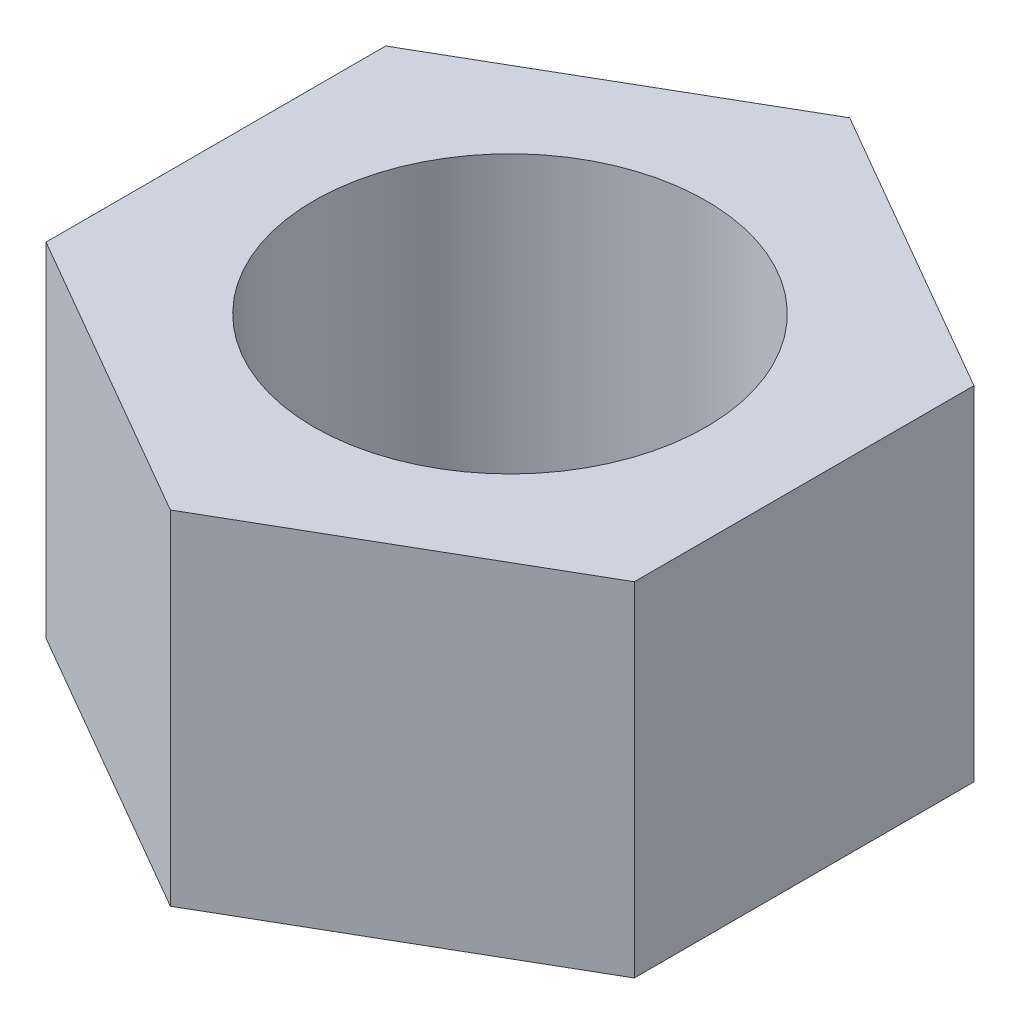
SolidWorks part; units mm, degrees
ref_plane "Front Plane" through (0, 0, 0) normal (0, 0, 1) x (1, 0, 0)
ref_plane "Top Plane" through (0, 0, 0) normal (0, 1, 0) x (1, 0, 0)
ref_plane "Right Plane" through (0, 0, 0) normal (1, 0, 0) x (0, 0, -1)
sketch "Sketch1" plane through (0, 0, 0) normal (0, 0, 1) x (1, 0, 0)
  line L0 (0, -4.1672) -> (0, 4.1672) construction
  line L1 (7.1438, 0) -> (-7.1438, 0) construction
  line L2 (4.7625, -4.1672) -> (-4.7625, -4.1672) construction
  line L3 (4.7625, -4.1672) -> (4.7625, -3.1089) construction
  point P4 (0, 0)
  point P8 (0, 0)
  point P11 (0, -4.1672)
  dimension "Height" = 8.3344
  dimension "Width" = 14.2875
  dimension "Thread Size" = 9.525
  dimension "Thread Pitch" = 1.0583
sketch "Sketch2" plane through (0, 0, 0) normal (1, 0, 0) x (0, 0, -1)
  line L0 (0, -4.1672) -> (0, 4.1672) construction
  line L1 (3.048, -1.9542) -> (-3.048, -1.9542)
  line L2 (3.048, -1.9542) -> (3.048, 4.1672)
  line L3 (3.048, 4.1672) -> (-3.048, 4.1672)
  line L4 (-3.048, -1.9542) -> (-3.048, 4.1672)
  line L5 (3.048, -1.9542) -> (-3.048, 4.1672) construction
  line L6 (3.048, 4.1672) -> (-3.048, -1.9542) construction
  point P0 (0, 1.1065)
  point P7 (0, 4.1672)
  dimension "Minimum Slot Width" = 6.096
  dimension "Minimum Slot Depth" = 6.1214
sketch "Sketch11" plane through (0, 0, 0) normal (0, 1, 0) x (1, 0, 0)
  line L1 (0, 8.2489) -> (-7.1438, 4.1244)
  line L2 (-7.1438, 4.1244) -> (-7.1438, -4.1244)
  line L3 (-7.1438, -4.1244) -> (0, -8.2489)
  line L4 (0, -8.2489) -> (7.1438, -4.1244)
  line L5 (7.1438, -4.1244) -> (7.1438, 4.1244)
  line L6 (7.1438, 4.1244) -> (0, 8.2489)
  circle A0 centre (0, 0) radius 7.1438 construction
  circle A1 centre (0, 0) radius 4.7625
  point P19 (0, -4.7625)
extrude "Boss-Extrude1" add sketch "Sketch11" along normal up to vertex (4.1672 mm away) and the other way up to vertex (4.1672 mm away) up to point (0, 4.1672, 0) other way up to point (0, -4.1672, 0)
fillet "Fillet1" [suppressed] radius 0.4286
sketch "Sketch3" plane through (0, 0, 0) normal (1, 0, 0) x (0, 0, -1)
  line L1 (4.1244, 4.1672) -> (8.2489, 4.1672) construction
  line L2 (6.4294, -4.1672) -> (8.2489, -3.1167)
  line L3 (4.1244, -4.1672) -> (8.2489, -4.1672) construction
  line L4 (8.2489, 4.1672) -> (8.2489, -4.1672) construction
  line L5 (8.2489, -3.1167) -> (8.2489, -4.1672)
  line L7 (6.7151, 4.1672) -> (8.2489, 3.2817)
  line L8 (8.2489, 3.2817) -> (8.2489, 4.1672)
  line L10 (6.4294, -4.1672) -> (8.2489, -4.1672)
  line L12 (6.7151, 0) -> (7.1438, 0) construction
  line L16 (6.7151, 4.1672) -> (8.2489, 4.1672)
  line L21 (4.7625, -4.1672) -> (4.7625, -3.9291)
  line L22 (-4.1244, -4.1672) -> (4.1244, -4.1672) construction
  line L24 (5.0006, -4.1672) -> (4.7625, -4.1672)
  line L25 (4.7625, -3.9291) -> (5.0006, -4.1672)
  line L26 (4.7625, 4.1672) -> (4.7625, 3.9291)
  line L27 (4.7625, 4.1672) -> (5.0006, 4.1672)
  line L28 (5.0006, 4.1672) -> (4.7625, 3.9291)
  line L29 (3.048, 4.1672) -> (-3.048, 4.1672) construction
  line L30 (5.0006, 0) -> (5.4293, 0) construction
  line L31 (6.2865, 0) -> (6.7151, 0) construction
  line L32 (5.4293, 0) -> (5.8579, 0) construction
  line L33 (5.8579, 0) -> (6.2865, 0) construction
  point P0 (6.7151, 4.1672)
  point P1 (7.1438, 0)
  point P14 (4.7625, 0)
  point P36 (7.1438, -4.1672)
  point P44 (6.9294, 0)
  dimension "D2" = 30
  dimension "D5" = 0.2381
  dimension "D7" = 0.7144
  dimension "D1" = 30
revolve "Cut-Revolve2" [suppressed] cut sketch "Sketch3" angle 360 about L0
sketch "Sketch15" [suppressed] plane through (15.4781, 0, 17.1852) normal (0.5, 0, -0.866) x (-0.866, 0, -0.5)
  line L0 (21.997, 3.9197) -> (21.997, 2.0011) construction
  line L1 (21.997, -1.8361) -> (21.997, 0.0825) construction
  line L2 (21.997, 0.0825) -> (21.997, 2.0011) construction
  line L3 (21.997, -1.8361) -> (21.997, -3.7547) construction
  line L6 (20.8893, 0.0825) -> (21.4432, -0.8768)
  line L7 (21.4432, -0.8768) -> (22.5509, -0.8768)
  line L8 (22.5509, -0.8768) -> (23.1048, 0.0825)
  line L9 (23.1048, 0.0825) -> (22.5509, 1.0418)
  line L10 (22.5509, 1.0418) -> (21.4432, 1.0418)
  line L11 (21.4432, 1.0418) -> (20.8893, 0.0825)
  circle A0 centre (21.997, 0.0825) radius 0.9593 construction
  spline S4 degree 3 poles (17.8726, 3.2817) (18.546, 3.4761) (19.2244, 3.6363) (20.5953, 3.8583) (21.2879, 3.9193) (22.3398, 3.9199) (22.6921, 3.905) (23.389, 3.8469) (23.7351, 3.8037) (24.7673, 3.6369) (25.4472, 3.4763) (26.1215, 3.2817) knots 0 0 0 0 0.25 0.25 0.5 0.5 0.625 0.625 0.75 0.75 1 1 1 1 construction
  spline S5 degree 3 poles (26.1215, -3.1167) (25.448, -3.3111) (24.7697, -3.4713) (23.3988, -3.6933) (22.7062, -3.7543) (21.6543, -3.755) (21.302, -3.74) (20.6051, -3.6819) (20.259, -3.6387) (19.2268, -3.472) (18.5469, -3.3113) (17.8726, -3.1167) knots 0 0 0 0 0.25 0.25 0.5 0.5 0.625 0.625 0.75 0.75 1 1 1 1 construction
  point P1 (21.997, 1.0418)
  point P6 (21.997, 0)
extrude "Cut-Extrude2" [suppressed] cut sketch "Sketch15" along normal blind 0.1905
sketch "Sketch18" [suppressed] plane through (0, 4.1672, 0) normal (0, 1, 0) x (1, 0, 0)
  line L0 (0, 0) -> (0, -6.7151) construction
  line L1 (0, 0) -> (-4.1421, -4.1421) construction
  line L2 (0, 0) -> (-1.5161, -5.6583) construction
  line L3 (-6.7151, 0) -> (-6.3722, 0) construction
  line L4 (-6.3722, 0) -> (-6.0293, 0) construction
  line L5 (-6.0293, 0) -> (-5.6864, 0) construction
  line L6 (-5.6864, 0) -> (-5.3435, 0) construction
  line L7 (-5.3435, 0) -> (-5.0006, 0) construction
  line L8 (0, 0) -> (-3.5719, -6.1867) construction
  line L9 (-7.1437, -4.1244) -> (0, -8.2489) construction
  circle A0 centre (0, 0) radius 6.7151 construction
  circle A1 centre (0, 0) radius 5.0006 construction
  arc A2 (-4.1421, -4.1421) -> (-1.5161, -5.6583) centre (0, 0) ccw construction
  arc A3 (-4.2634, -4.2634) -> (-1.5605, -5.8239) centre (0, 0) ccw
  arc A4 (-4.0209, -4.0209) -> (-1.4718, -5.4927) centre (0, 0) ccw
  arc A5 (-4.0209, -4.0209) -> (-4.2634, -4.2634) centre (-4.1421, -4.1421) ccw
  arc A6 (-1.5605, -5.8239) -> (-1.4718, -5.4927) centre (-1.5161, -5.6583) ccw
  arc A7 (4.1421, -4.1421) -> (1.5161, -5.6583) centre (0, 0) cw construction
  arc A8 (4.2634, -4.2634) -> (1.5605, -5.8239) centre (0, 0) cw
  arc A9 (4.0209, -4.0209) -> (1.4718, -5.4927) centre (0, 0) cw
  arc A10 (4.0209, -4.0209) -> (4.2634, -4.2634) centre (4.1421, -4.1421) cw
  arc A11 (1.5605, -5.8239) -> (1.4718, -5.4927) centre (1.5161, -5.6583) cw
  point P18 (-2.9289, -5.0731)
  point P30 (2.9289, -5.0731)
  dimension "D1" = 30
extrude "Cut-Extrude3" [suppressed] cut sketch "Sketch18" against normal blind 0.2381
sketch "Sketch5" [suppressed] plane through (0, 0, 0) normal (0, 1, 0) x (1, 0, 0)
  circle A1 centre (0, 0) radius 4.7625 construction
  point P0 (0, -4.7625)
sketch "Sketch6" [suppressed] plane through (0, 0, 0) normal (0, 0, 1) x (1, 0, 0)
  line L0 (4.7625, 4.1672) -> (4.7625, -4.1672)
  line L2 (0, -4.1672) -> (7.1438, -4.1672) construction
  line L3 (4.7625, -4.1672) -> (0, -4.1672)
  line L4 (0, -4.1672) -> (0, 4.1672)
  line L5 (0, -4.1672) -> (0, 4.1672) construction
  line L6 (0, 4.1672) -> (4.7625, 4.1672)
revolve "Revolve2" [suppressed] add sketch "Sketch6" angle 360 about L4
sketch "Sketch7" [suppressed] plane through (0, -4.1672, 0) normal (0, -1, 0) x (1, 0, 0)
  circle A2 centre (0, 0) radius 4.7625
  circle A3 centre (0, 0) radius 4.7625
  dimension "D1" = 0
curve "Helix/Spiral1" [suppressed] pitch 1.0583 height 8.3344 turns 7.875
sketch "Sketch8" [suppressed] plane through (0, 0, 0) normal (0, 0, 1) x (1, 0, 0)
  line L0 (4.8771, -4.101) -> (3.9605, -4.6302) construction
  line L1 (3.9605, -4.6302) -> (4.8771, -5.1594) construction
  line L2 (4.8771, -5.1594) -> (4.8771, -4.101) construction
  line L3 (4.0751, -4.5641) -> (4.0751, -4.6964)
  line L4 (4.7625, -4.1672) -> (4.7625, -5.0932) construction
  line L5 (4.7625, -4.6302) -> (4.8771, -4.6302) construction
  line L6 (3.9605, -4.6302) -> (4.0751, -4.6302) construction
  line L7 (4.8198, -4.6302) -> (4.8198, -5.1263) construction
  line L8 (4.0751, -4.5641) -> (4.8771, -4.101)
  line L9 (4.8771, -4.101) -> (4.8198, -5.1263)
  line L10 (4.0751, -4.6964) -> (4.8198, -5.1263)
  dimension "D1" = 1.0583
  dimension "D2" = 0.1323
sweep "Cut-Sweep1" [suppressed] cut profiles "Sketch8" path "Helix/Spiral1"
sketch "Sketch9" [suppressed] plane through (0, 0, 0) normal (0, 0, 1) x (1, 0, 0)
  line L0 (0, 0.5953) -> (0, -4.1672)
  line L1 (0, 0.5953) -> (0, 0.8334)
  line L2 (0, -4.1672) -> (4.7625, -4.1672)
  line L3 (4.7625, -4.1672) -> (5.0006, -4.1672)
  line L4 (5.0006, -4.1672) -> (0, 0.8334)
  dimension "D1" = 0.2381
revolve "Revolve3" [suppressed] add sketch "Sketch9" angle 360 about L0
sketch "Sketch14" [suppressed] plane through (0, 0, 0) normal (0, 0, 1) x (1, 0, 0)
  line L0 (5.0006, 4.1672) -> (0, 4.1672)
  line L1 (0, 4.1672) -> (0, -0.8334)
  line L2 (0, -0.8334) -> (5.0006, 4.1672)
revolve "Revolve4" [suppressed] add sketch "Sketch14" angle 360 about L1
sketch "Sketch10" [suppressed] plane through (0, -4.1672, 0) normal (0, -1, 0) x (1, 0, 0)
  circle A0 centre (0, 0) radius 5.0006 construction
  circle A1 centre (0, 0) radius 5.0006
extrude "Boss-Extrude2" [suppressed] add sketch "Sketch10" against normal up to surface (8.3344 mm away) up to face at (0, 4.1672, 0)
combine bodies "Combine1" [suppressed] operation type subtract main body 110 bodies to subtract 120
equation "\"D5@Sketch3\"=\"Thread Size@Sketch1\"*.025"
equation "\"D4@Helix/Spiral1\" = \"Thread Pitch@Sketch1\""
equation "\"D3@Helix/Spiral1\" = \"Height@Sketch1\""
equation "\"D1@Sketch8\" = \"Thread Pitch@Sketch1\""
equation "\"D2@Sketch8\" = \"Thread Pitch@Sketch1\" / 8"
equation "\"D1@Sketch9\"=\"Thread Size@Sketch1\" * .025"
equation "\"D1@Fillet1\"=\"Width@Sketch1\" * .03"
equation "\"D7@Sketch3\"=\"Width@Sketch1\"*.05"
equation "\"D1@Cut-Extrude2\" =  (  ( \"Width@Sketch1\" - \"Thread Size@Sketch1\" / 2 )  * .02 ) "
equation "\"D1@Cut-Extrude3\"=((\"width@sketch1\"-\"Thread Size@sketch1\"/2)*.025)"
